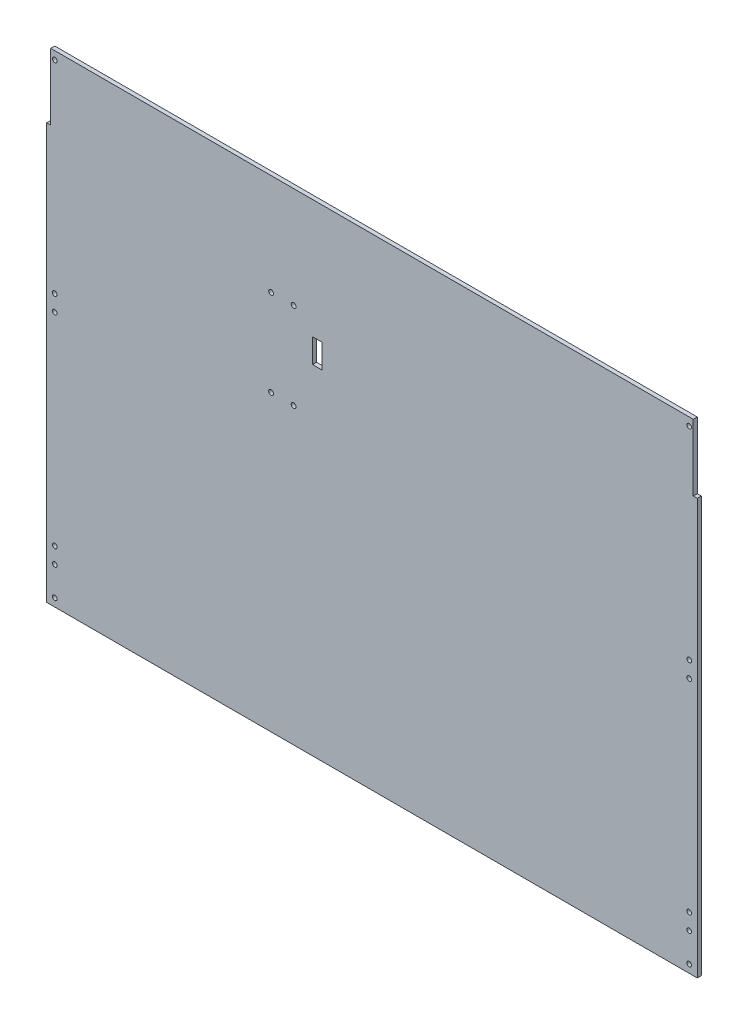
SolidWorks part; units mm, degrees
ref_plane "Front Plane" through (0, 0, 0) normal (0, 0, 1) x (1, 0, 0)
ref_plane "Top Plane" through (0, 0, 0) normal (0, 1, 0) x (1, 0, 0)
ref_plane "Right Plane" through (0, 0, 0) normal (1, 0, 0) x (0, 0, -1)
sketch "Sketch1" plane through (0, 0, 0) normal (0, 0, 1) x (1, 0, 0)
  line L1 (-254, -190.5) -> (254, -190.5)
  line L2 (-254, -190.5) -> (-254, 190.5)
  line L3 (-254, 190.5) -> (254, 190.5)
  line L4 (254, -190.5) -> (254, 190.5)
  line L5 (-254, -190.5) -> (254, 190.5) construction
  line L6 (-254, 190.5) -> (254, -190.5) construction
  point P0 (0, 0)
  dimension "D1" = 508
  dimension "D2" = 381
extrude "Boss-Extrude1" add sketch "Sketch1" along normal blind 3.175
sketch "Sketch3" plane through (0, 0, 3.175) normal (0, 0, 1) x (1, 0, 0)
  line L0 (-254, 190.5) -> (-254, -190.5) construction
  line L1 (-46.99, 77.47) -> (-39.37, 77.47)
  line L2 (-46.99, 77.47) -> (-46.99, 96.52)
  line L3 (-46.99, 96.52) -> (-39.37, 96.52)
  line L4 (-39.37, 77.47) -> (-39.37, 96.52)
  line L5 (254, 190.5) -> (-254, 190.5) construction
  dimension "D1" = 207.01
  dimension "D2" = 7.62
  dimension "D3" = 113.03
  dimension "D4" = 19.05
extrude "Cut-Extrude2" cut sketch "Sketch3" against normal up to surface (3.175 mm away) up to face at (0, 0, 0)
sketch "Sketch2" plane through (0, 0, 3.175) normal (0, 0, 1) x (1, 0, 0)
  line L0 (-250.825, 190.5) -> (-250.825, -190.5) construction
  line L1 (254, 190.5) -> (-254, 190.5) construction
  line L2 (-254, -190.5) -> (254, -190.5) construction
  line L3 (250.825, 190.5) -> (250.825, -190.5) construction
  line L4 (254, -190.5) -> (254, 190.5) construction
  line L5 (-254, 190.5) -> (-254, -190.5) construction
  line L6 (0, 0) -> (0, -50000) construction
  line L8 (-39.37, 96.52) -> (-46.99, 96.52) construction
  circle A0 centre (-250.825, -184.15) radius 1.8542
  circle A1 centre (-250.825, 184.15) radius 1.8542
  circle A2 centre (250.825, 184.15) radius 1.8542
  circle A3 centre (250.825, -184.15) radius 1.8542
  circle A4 centre (-250.825, 24.13) radius 1.8542
  circle A5 centre (250.825, 24.13) radius 1.8542
  circle A6 centre (-250.825, 11.43) radius 1.8542
  circle A7 centre (-250.825, -148.59) radius 1.8542
  circle A8 centre (-250.825, -161.29) radius 1.8542
  circle A9 centre (250.825, -161.29) radius 1.8542
  circle A10 centre (250.825, -148.59) radius 1.8542
  circle A11 centre (250.825, 11.43) radius 1.8542
  circle A12 centre (-79.7747, 110.49) radius 1.905
  circle A13 centre (-79.7747, 41.91) radius 1.905
  circle A14 centre (-61.9947, 110.49) radius 1.905
  circle A15 centre (-61.9947, 41.91) radius 1.905
  point P33 (0, -190.5)
  dimension "D3" = 3.7084
  dimension "D10" = 12.7
  dimension "D14" = 3.81
  dimension "D12" = 17.78
  dimension "D1" = 3.175
  dimension "D2" = 3.175
  dimension "D4" = 6.35
  dimension "D5" = 6.35
  dimension "D6" = 6.35
  dimension "D7" = 6.35
  dimension "D8" = 160.02
  dimension "D9" = 160.02
  dimension "D11" = 29.21
  dimension "D13" = 68.58
  dimension "D15" = 15.0047
  dimension "D16" = 13.97
extrude "Cut-Extrude1" cut sketch "Sketch2" against normal blind 3.175
sketch "Sketch4" plane through (0, 0, 3.175) normal (0, 0, 1) x (1, 0, 0)
  line L0 (254, -190.5) -> (254, 190.5) construction
  line L1 (254, 137.9538) -> (257.175, 137.9538)
  line L2 (254, 137.9538) -> (254, -190.5)
  line L3 (254, -190.5) -> (257.175, -190.5)
  line L4 (257.175, 137.9538) -> (257.175, -190.5)
  line L5 (-254, -190.5) -> (254, -190.5) construction
  line L6 (254, 190.5) -> (-254, 190.5) construction
  line L7 (0, 190.5) -> (0, -190.5) construction
  line L8 (-254, -190.5) -> (-257.175, -190.5)
  line L9 (-254, 137.9538) -> (-257.175, 137.9538)
  line L10 (-254, 137.9538) -> (-254, -190.5)
  line L11 (-257.175, 137.9538) -> (-257.175, -190.5)
  dimension "D1" = 3.175
  dimension "D2" = 52.5463
extrude "Boss-Extrude2" add sketch "Sketch4" against normal blind 3.175
